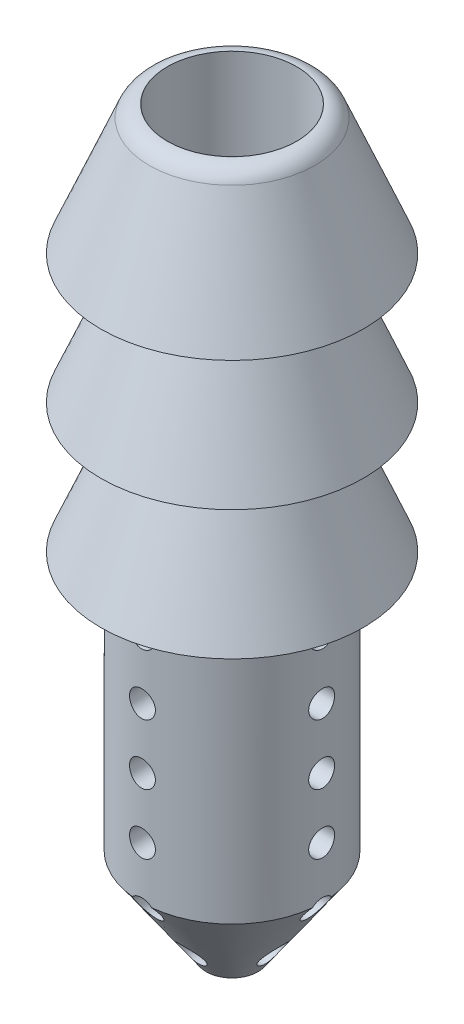
SolidWorks part; units mm, degrees
ref_plane "Front Plane" through (0, 0, 0) normal (0, 0, 1) x (1, 0, 0)
ref_plane "Top Plane" through (0, 0, 0) normal (0, 1, 0) x (1, 0, 0)
ref_plane "Right Plane" through (0, 0, 0) normal (1, 0, 0) x (0, 0, -1)
sketch "Sketch1" plane through (0, 0, 0) normal (0, 1, 0) x (1, 0, 0)
  circle A0 centre (0, 0) radius 5.08
  dimension "D1" = 10.16
extrude "Boss-Extrude1" add sketch "Sketch1" along normal blind 5 draft 22.5
sketch "Sketch2" plane through (0, 0, 0) normal (1, 0, 0) x (0, 0, -1)
  line L0 (0, 0) -> (0, 3.9361) construction
pattern_linear "LPattern1" count 3 spacing 5 along (0, -1, 0) of "Boss-Extrude1"
sketch "Sketch3" plane through (0, -10, 0) normal (0, -1, 0) x (1, 0, 0)
  circle A0 centre (0, 0) radius 3.5
  circle A1 centre (0, 0) radius 2.5
  dimension "D1" = 7
  dimension "D2" = 5
extrude "Boss-Extrude2" add sketch "Sketch3" along normal blind 10
sketch "Sketch4" plane through (0, 0, 0) normal (1, 0, 0) x (0, 0, -1)
  line L0 (-3.5, -20) -> (3.5, -20) construction
  line L1 (-3.5, -20) -> (3.5, -20)
  line L2 (-3.5, -20) -> (0, -25)
  line L3 (0, -25) -> (0, -20)
  line L4 (-2.5, -20) -> (0, -23.5714)
  line L5 (-2.5, -20) -> (2.5, -20) construction
  line L6 (-2.5, -20) -> (2.5, -20)
  point P8 (-2.456, -16)
  dimension "D1" = 5
revolve "Revolve2" add sketch "Sketch4" angle 360 about L0 region at (0, -22.1627, 1.5139)
sketch "Sketch5" plane through (0, 0, 0) normal (0, 0, 1) x (1, 0, 0)
  line L0 (0, -200000) -> (0, 200003.9361) construction
  line L1 (2.5, -20) -> (-2.5, -20) construction
  line L2 (-2.5, -20) -> (2.5, -20)
  line L4 (2.5, -20) -> (-2.5, -20)
  circle A0 centre (0, -11) radius 0.5
  point P6 (0, -15.8931)
  point P7 (0, -15.7061)
  point P8 (0, -13.505)
  point P9 (0, -7.375)
  point P10 (0, -7.0098)
  point P11 (0, -9.0997)
  point P12 (0, -6.7846)
  dimension "D2" = 1
  dimension "D3" = 9
extrude "Cut-Extrude1" cut sketch "Sketch5" against normal through all both and the other way through all contours A0 region at (0, -11, 0)
ref_plane "Plane1" through (0, -25, 0) normal (0, 1, 0) x (1, 0, 0)
pattern_linear "LPattern2" count 7 spacing 2.3333 along (0, -1, 0) of "Cut-Extrude1"
pattern_circular "CirPattern1" count 2 every 90 about axis through (0, -20, 0) along (0, -1, 0) of "LPattern2"
sketch "Sketch6" plane through (0, -10, 0) normal (0, -1, 0) x (1, 0, 0)
  circle A1 centre (0, 0) radius 2.5
  circle A2 centre (0, 0) radius 2.5
  dimension "D1" = 0
extrude "Cut-Extrude2" cut sketch "Sketch6" against normal up to surface (15 mm away) up to face at (0, 5, 3.0089)
sketch "Sketch7" plane through (0, -25, 0) normal (0, 1, 0) x (1, 0, 0)
  circle A0 centre (0, 0) radius 1
  dimension "D1" = 2
extrude "Cut-Extrude3" cut sketch "Sketch7" along normal through all
chamfer "Chamfer1" distance 0.75 angle 45 3 edges at (0, 0, 3.0089) (0, -10, 3.5) (0, -5, 3.0089) first distance on face at (0, 0, 3.0089) first distance on face at (0, -10, 3.5) first distance on face at (0, -5, 3.0089)
fillet "Fillet1" radius 0.75 1 edges at (0, 5, 3.0089)
equation "\"TUBEID\"=10.16"
equation "\"D1@Sketch1\"=\"TUBEID\""
equation "\"H\"= 5"
equation "\"D1@Boss-Extrude1\"=\"H\""
equation "\"D3@LPattern1\"=\"H\""
equation "\"NOZZLEOD\"=6.04576"
equation "\"NOZZLEID\"=4.25729"
equation "\"L\"=10"
equation "\"D1@Boss-Extrude2\"=\"L\""
equation "\"NOZZLEL\"=5"
equation "\"D1@Sketch4\"=\"NOZZLEL\""
equation "\"NOZZLEHD\"=1"
equation "\"D2@Sketch5\"=\"NOZZLEHD\""
equation "\"D3@Sketch5\"=\"L\"-\"NOZZLEHD\""
equation "\"CH\"=0.75"
equation "\"D1@Chamfer1\"=\"CH\""
equation "\"D1@Fillet1\"=\"CH\""
